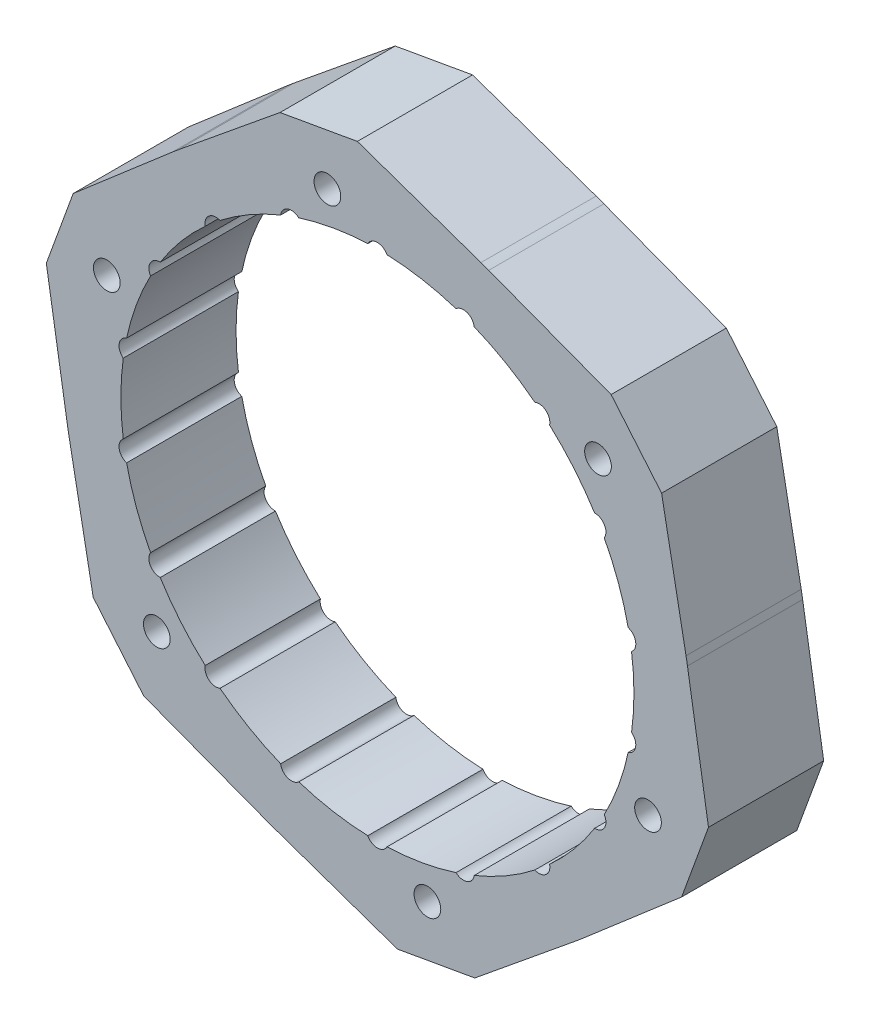
SolidWorks part; units mm, degrees
ref_plane "Front Plane" through (0, 0, 0) normal (0, 0, 1) x (1, 0, 0)
ref_plane "Top Plane" through (0, 0, 0) normal (0, 1, 0) x (1, 0, 0)
ref_plane "Right Plane" through (0, 0, 0) normal (1, 0, 0) x (0, 0, -1)
sketch "Sketch1" plane through (0, 0, 0) normal (0, 0, 1) x (1, 0, 0)
  line L0 (-16.417, 45.1052) -> (0, 0) construction
  line L1 (0, 0) -> (-8.3351, 47.2708) construction
  circle A2 centre (0, 0) radius 60
  arc A36 (-15.0158, 46.6425) -> (-18.4784, 45.3822) centre (-16.417, 45.1052) ccw
  arc A40 (-32.8857, 36.3254) -> (-41.484, 26.0783) centre (0, 0) ccw
  arc A42 (-2.0783, 47.9149) -> (-14.435, 45.7361) centre (0, 0) ccw construction
  arc A58 (-18.4784, 45.3822) -> (-30.0629, 38.6939) centre (0, 0) ccw
  arc A59 (-1.8424, 48.9653) -> (-15.0158, 46.6425) centre (0, 0) ccw
  circle A60 centre (0, 0) radius 48 construction
  arc A61 (1.8424, 48.9653) -> (-1.8424, 48.9653) centre (0, 48) ccw
  arc A62 (14.435, 45.7361) -> (2.0783, 47.915) centre (0, 0) ccw construction
  arc A63 (18.4784, 45.3822) -> (15.0158, 46.6425) centre (16.417, 45.1052) ccw
  arc A64 (29.2071, 38.0409) -> (18.3408, 44.3145) centre (0, 0) ccw construction
  arc A65 (32.8857, 36.3254) -> (30.0629, 38.6939) centre (30.8538, 36.7701) ccw
  arc A66 (40.4564, 25.7573) -> (32.3912, 35.3691) centre (0, 0) ccw construction
  arc A67 (43.3264, 22.8871) -> (41.484, 26.0783) centre (41.5692, 24) ccw
  arc A68 (46.8261, 10.367) -> (42.5347, 22.1576) centre (0, 0) ccw construction
  arc A69 (48.5414, 6.6883) -> (47.9015, 10.3172) centre (47.2708, 8.3351) ccw
  arc A70 (47.5479, -6.2737) -> (47.5479, 6.2737) centre (0, 0) ccw construction
  arc A71 (47.9015, -10.3172) -> (48.5414, -6.6883) centre (47.2708, -8.3351) ccw
  arc A72 (42.5347, -22.1576) -> (46.8261, -10.367) centre (0, 0) ccw construction
  arc A73 (41.484, -26.0783) -> (43.3264, -22.8871) centre (41.5692, -24) ccw
  arc A74 (32.3912, -35.3691) -> (40.4564, -25.7573) centre (0, 0) ccw construction
  arc A75 (30.0629, -38.6939) -> (32.8857, -36.3254) centre (30.8538, -36.7701) ccw
  arc A76 (18.3408, -44.3145) -> (29.2071, -38.0409) centre (0, 0) ccw construction
  arc A77 (15.0158, -46.6425) -> (18.4784, -45.3822) centre (16.417, -45.1052) ccw
  arc A78 (2.0783, -47.9149) -> (14.435, -45.7361) centre (0, 0) ccw construction
  arc A79 (-1.8424, -48.9654) -> (1.8424, -48.9654) centre (0, -48) ccw
  arc A80 (-14.435, -45.7361) -> (-2.0783, -47.9149) centre (0, 0) ccw construction
  arc A81 (-18.4784, -45.3822) -> (-15.0158, -46.6425) centre (-16.417, -45.1052) ccw
  arc A82 (-29.2071, -38.0409) -> (-18.3408, -44.3145) centre (0, 0) ccw construction
  arc A83 (-32.8857, -36.3254) -> (-30.0629, -38.6939) centre (-30.8538, -36.7701) ccw
  arc A84 (-40.4564, -25.7573) -> (-32.3912, -35.3691) centre (0, 0) ccw construction
  arc A85 (-43.3264, -22.8871) -> (-41.484, -26.0783) centre (-41.5692, -24) ccw
  arc A86 (-46.8261, -10.367) -> (-42.5347, -22.1576) centre (0, 0) ccw construction
  arc A87 (-48.5414, -6.6883) -> (-47.9015, -10.3172) centre (-47.2708, -8.3351) ccw
  arc A88 (-47.5479, 6.2737) -> (-47.5479, -6.2737) centre (0, 0) ccw construction
  arc A89 (-47.9015, 10.3172) -> (-48.5414, 6.6883) centre (-47.2708, 8.3351) ccw
  arc A90 (-42.5347, 22.1576) -> (-46.8261, 10.367) centre (0, 0) ccw construction
  arc A91 (-41.484, 26.0783) -> (-43.3264, 22.8871) centre (-41.5692, 24) ccw
  arc A92 (-32.3912, 35.3691) -> (-40.4564, 25.7573) centre (0, 0) ccw construction
  arc A93 (-30.0629, 38.6939) -> (-32.8857, 36.3254) centre (-30.8538, 36.7701) ccw
  arc A94 (-18.3408, 44.3145) -> (-29.2071, 38.0409) centre (0, 0) ccw construction
  arc A95 (15.0158, 46.6425) -> (1.8424, 48.9653) centre (0, 0) ccw
  arc A96 (30.0629, 38.6939) -> (18.4784, 45.3822) centre (0, 0) ccw
  arc A97 (41.484, 26.0783) -> (32.8857, 36.3254) centre (0, 0) ccw
  arc A98 (47.9015, 10.3172) -> (43.3264, 22.8871) centre (0, 0) ccw
  arc A99 (48.5414, -6.6883) -> (48.5414, 6.6883) centre (0, 0) ccw
  arc A100 (43.3264, -22.8871) -> (47.9015, -10.3172) centre (0, 0) ccw
  arc A101 (32.8857, -36.3254) -> (41.484, -26.0783) centre (0, 0) ccw
  arc A102 (18.4784, -45.3822) -> (30.0629, -38.6939) centre (0, 0) ccw
  arc A103 (1.8424, -48.9654) -> (15.0158, -46.6425) centre (0, 0) ccw
  arc A104 (-15.0158, -46.6425) -> (-1.8424, -48.9654) centre (0, 0) ccw
  arc A105 (-30.0629, -38.6939) -> (-18.4784, -45.3822) centre (0, 0) ccw
  arc A106 (-41.484, -26.0783) -> (-32.8857, -36.3254) centre (0, 0) ccw
  arc A107 (-47.9015, -10.3172) -> (-43.3264, -22.8871) centre (0, 0) ccw
  arc A108 (-48.5414, 6.6883) -> (-48.5414, -6.6883) centre (0, 0) ccw
  arc A109 (-43.3264, 22.8871) -> (-47.9015, 10.3172) centre (0, 0) ccw
  point P59 (0, 0)
  point P85 (0, 0)
  dimension "D1" = 2.08
  dimension "D2" = 47.96
  dimension "D3" = 120
  dimension "D6" = 98
  dimension "D5" = 18
  dimension "D4" = 10
extrude "Boss-Extrude1" add sketch "Sketch1" along normal blind 22
sketch "Sketch2" plane through (0, 0, 22) normal (0, 0, 1) x (1, 0, 0)
  line L0 (0, 0) -> (0, 60) construction
  line L1 (0, 0) -> (-9.5506, 54.1644) construction
  circle A0 centre (0, 0) radius 55 construction
  circle A1 centre (-9.5506, 54.1644) radius 2.55
  circle A2 centre (0, 0) radius 60 construction
  circle A3 centre (42.1324, 35.3533) radius 2.55
  circle A4 centre (51.6831, -18.8111) radius 2.55
  circle A5 centre (9.5506, -54.1644) radius 2.55
  circle A6 centre (-42.1324, -35.3533) radius 2.55
  circle A7 centre (-51.6831, 18.8111) radius 2.55
  point P22 (0, 0)
  dimension "D1" = 110
  dimension "D2" = 5.1
  dimension "D3" = 10
  dimension "D4" = 6
extrude "Cut-Extrude2" cut sketch "Sketch2" against normal through all
sketch "Sketch3" plane through (0, 0, 22) normal (0, 0, 1) x (1, 0, 0)
  line L0 (0, 0) -> (-9.5506, 54.1644) construction
  line L1 (-9.5506, 54.1644) -> (-11.2871, 64.0125) construction
  line L2 (0, 65) -> (0, 0) construction
  line L3 (-37.9588, 46.4664) -> (-18.5978, 62.2826)
  line L4 (-18.5978, 62.2826) -> (-3.8257, 64.8873)
  line L5 (-3.8257, 64.8873) -> (19.7772, 56.6468)
  line L6 (54.2812, 35.7568) -> (58.9462, 11.1959)
  line L7 (44.6394, 47.2475) -> (54.2812, 35.7568)
  line L8 (21.2617, 56.1065) -> (44.6394, 47.2475)
  line L9 (58.1069, -29.1305) -> (39.169, -45.4509)
  line L10 (63.2372, -15.0351) -> (58.1069, -29.1305)
  line L11 (59.2205, 9.6401) -> (63.2372, -15.0351)
  line L12 (3.8257, -64.8873) -> (-19.7772, -56.6468)
  line L13 (18.5978, -62.2826) -> (3.8257, -64.8873)
  line L14 (37.9588, -46.4664) -> (18.5978, -62.2826)
  line L15 (-54.2812, -35.7568) -> (-58.9462, -11.1959)
  line L16 (-44.6394, -47.2475) -> (-54.2812, -35.7568)
  line L17 (-21.2617, -56.1065) -> (-44.6394, -47.2475)
  line L18 (-58.1069, 29.1305) -> (-39.169, 45.4509)
  line L19 (-63.2372, 15.0351) -> (-58.1069, 29.1305)
  line L20 (-59.2205, -9.6401) -> (-63.2372, 15.0351)
  circle A0 centre (0, 0) radius 65 construction
  circle A1 centre (0, 0) radius 60 construction
  arc A2 (-37.9588, 46.4664) -> (19.7772, 56.6468) centre (0, 0) cw
  arc A3 (21.2617, 56.1065) -> (58.9462, 11.1959) centre (0, 0) cw
  arc A4 (59.2205, 9.6401) -> (39.169, -45.4509) centre (0, 0) cw
  arc A5 (37.9588, -46.4664) -> (-19.7772, -56.6468) centre (0, 0) cw
  arc A6 (-21.2617, -56.1065) -> (-58.9462, -11.1959) centre (0, 0) cw
  arc A7 (-59.2205, -9.6401) -> (-39.169, 45.4509) centre (0, 0) cw
  point P11 (-11.2117, 63.585)
  point P38 (0, 0)
  dimension "D1" = 130
  dimension "D2" = 15
  dimension "D3" = 6
extrude "Boss-Extrude2" add sketch "Sketch3" against normal blind 22
